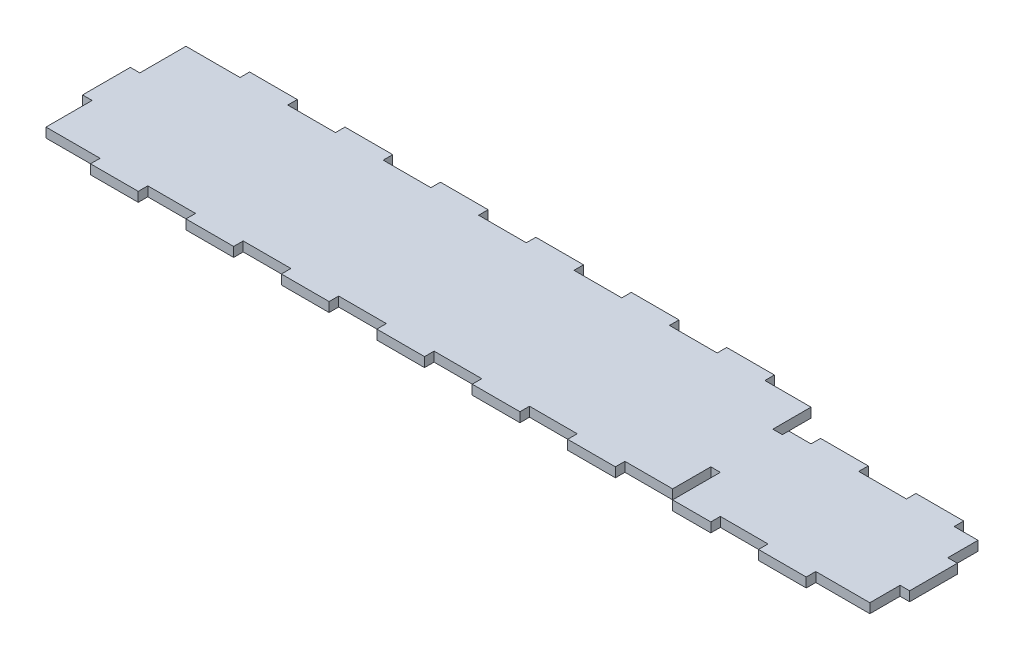
SolidWorks part; units mm, degrees
ref_plane "Alzado" through (0, 0, 0) normal (0, 0, 1) x (1, 0, 0)
ref_plane "Planta" through (0, 0, 0) normal (0, 1, 0) x (1, 0, 0)
ref_plane "Vista lateral" through (0, 0, 0) normal (1, 0, 0) x (0, 0, -1)
sketch "Croquis1" plane through (0, 0, 0) normal (0, 1, 0) x (1, 0, 0)
  line L1 (20, 50) -> (35, 50)
  line L2 (197, 3) -> (200, 3)
  line L3 (20, 0) -> (35, 0)
  line L4 (265, 12.5) -> (265, 27.5)
  line L5 (254.5, 40) -> (239.5, 40)
  line L6 (0, 25) -> (0, 32.5)
  line L7 (0, 32.5) -> (3, 32.5)
  line L8 (3, 32.5) -> (3, 47)
  line L9 (200, 15) -> (203, 15)
  line L10 (110, 47) -> (95, 47)
  line L11 (95, 47) -> (95, 50)
  line L12 (95, 50) -> (80, 50)
  line L13 (80, 50) -> (80, 47)
  line L14 (80, 47) -> (65, 47)
  line L15 (65, 47) -> (65, 50)
  line L16 (65, 50) -> (50, 50)
  line L17 (50, 50) -> (50, 47)
  line L18 (50, 47) -> (35, 47)
  line L19 (35, 47) -> (35, 50)
  line L20 (35, 50) -> (20, 50)
  line L21 (20, 50) -> (20, 47)
  line L22 (20, 47) -> (3, 47)
  line L23 (185, 47) -> (196.5, 47)
  line L24 (185, 50) -> (185, 47)
  line L25 (170, 47) -> (170, 50)
  line L26 (155, 47) -> (170, 47)
  line L27 (155, 50) -> (155, 47)
  line L28 (140, 47) -> (140, 50)
  line L29 (125, 47) -> (140, 47)
  line L30 (125, 50) -> (125, 47)
  line L31 (110, 47) -> (110, 50)
  line L32 (0, 25) -> (0, 17.5)
  line L33 (203, 15) -> (203, 0)
  line L34 (0, 17.5) -> (3, 17.5)
  line L35 (3, 17.5) -> (3, 3)
  line L36 (224.5, 40) -> (209.5, 40)
  line L37 (140, 3) -> (125, 3)
  line L38 (125, 3) -> (125, 0)
  line L39 (125, 0) -> (110, 0)
  line L40 (110, 0) -> (110, 3)
  line L41 (110, 3) -> (95, 3)
  line L42 (95, 3) -> (95, 0)
  line L43 (95, 0) -> (80, 0)
  line L44 (80, 0) -> (80, 3)
  line L45 (80, 3) -> (65, 3)
  line L46 (65, 3) -> (65, 0)
  line L47 (65, 0) -> (50, 0)
  line L48 (50, 0) -> (50, 3)
  line L49 (50, 3) -> (35, 3)
  line L50 (35, 3) -> (35, 0)
  line L51 (35, 0) -> (20, 0)
  line L52 (20, 0) -> (20, 3)
  line L53 (20, 3) -> (3, 3)
  line L54 (245, 3) -> (262, 3)
  line L55 (245, 0) -> (245, 3)
  line L56 (230, 3) -> (230, 0)
  line L57 (215, 3) -> (230, 3)
  line L58 (215, 0) -> (215, 3)
  line L60 (185, 3) -> (197, 3)
  line L61 (185, 0) -> (185, 3)
  line L62 (170, 3) -> (170, 0)
  line L63 (155, 3) -> (170, 3)
  line L64 (155, 0) -> (155, 3)
  line L65 (140, 3) -> (140, 0)
  line L66 (254.5, 40) -> (239.5, 40)
  line L67 (199.5, 35) -> (202.5, 35)
  line L68 (224.5, 37) -> (239.5, 37)
  line L69 (239.5, 37) -> (239.5, 40)
  line L70 (239.5, 40) -> (254.5, 40)
  line L71 (254.5, 40) -> (254.5, 37)
  line L72 (254.5, 37) -> (262, 37)
  line L73 (209.5, 37) -> (202.5, 37)
  line L74 (209.5, 40) -> (209.5, 37)
  line L75 (224.5, 37) -> (224.5, 40)
  line L76 (202.5, 35) -> (202.5, 37)
  line L78 (265, 20) -> (265, 27.5)
  line L79 (265, 27.5) -> (262, 27.5)
  line L80 (262, 27.5) -> (262, 37)
  line L81 (265, 20) -> (265, 12.5)
  line L82 (265, 12.5) -> (262, 12.5)
  line L83 (262, 12.5) -> (262, 3)
  line L85 (196.5, 47) -> (199.5, 47)
  line L87 (199.5, 35) -> (199.5, 37)
  line L89 (200, 15) -> (200, 3)
  line L90 (0, 17.5) -> (0, 32.5)
  line L91 (50, 0) -> (65, 0)
  line L92 (80, 0) -> (95, 0)
  line L93 (110, 0) -> (125, 0)
  line L94 (140, 0) -> (155, 0)
  line L95 (170, 0) -> (185, 0)
  line L96 (203, 0) -> (215, 0)
  line L97 (230, 0) -> (245, 0)
  line L98 (170, 50) -> (185, 50)
  line L99 (140, 50) -> (155, 50)
  line L100 (50, 50) -> (65, 50)
  line L101 (80, 50) -> (95, 50)
  line L102 (110, 50) -> (125, 50)
  line L103 (199.5, 47) -> (199.5, 37)
  dimension "D3" = 17
  dimension "D4" = 3
  dimension "D5" = 7.5
  dimension "D6" = 3
  dimension "D7" = 11.5
  dimension "D9" = 15
  dimension "D10" = 15
  dimension "D11" = 15
  dimension "D12" = 15
  dimension "D13" = 15
  dimension "D14" = 7.5
  dimension "D17" = 15
  dimension "D18" = 15
  dimension "D19" = 15
  dimension "D20" = 15
  dimension "D21" = 15
  dimension "D22" = 15
  dimension "D23" = 15
  dimension "D26" = 15
  dimension "D27" = 7.5
  dimension "D28" = 3
  dimension "D29" = 7.5
extrude "Saliente-Extruir1" add sketch "Croquis1" along normal blind 3 contours L102 L31 L10 L11 L12 L13 L14 L15 L16 L17 L18 L19 L1 L21 L22 L8 L7 L6 L32 L34 L35 L53 L52 L3 L50 L49 L48 L47 L46 L45 L44 L43 L42 L41 L40 L39 L38 L37 L65 L94 L64 L63 L62 L95 L61 L60 L89 L96 region at (126.9434, 0, -24.0435)
